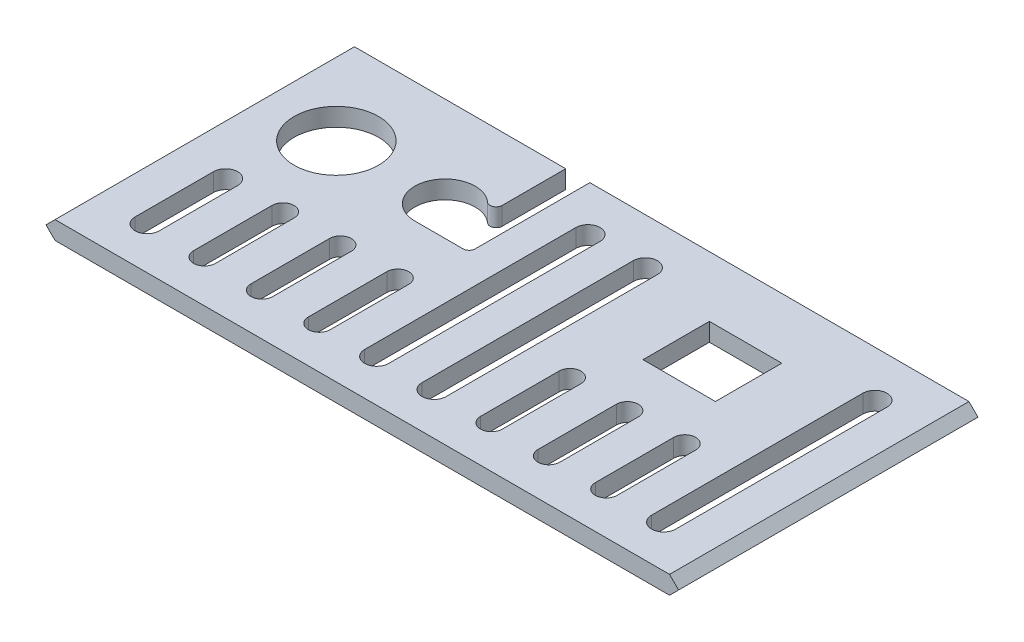
SolidWorks part; units mm, degrees
ref_plane "前视基准面" through (0, 0, 0) normal (0, 0, 1) x (1, 0, 0)
ref_plane "上视基准面" through (0, 0, 0) normal (0, 1, 0) x (1, 0, 0)
ref_plane "右视基准面" through (0, 0, 0) normal (1, 0, 0) x (0, 0, -1)
sketch "Sketch4" plane through (0, 0, 0) normal (0, 0, 1) x (1, 0, 0)
  line L0 (-50.9, 0) -> (50.9, 0)
  line L1 (-50.9, 0) -> (-52.4, -1.5)
  line L2 (-52.4, -1.5) -> (-50.9, -3)
  line L3 (-50.9, -3) -> (50.9, -3)
  line L4 (50.9, -3) -> (52.4, -1.5)
  line L5 (52.4, -1.5) -> (50.9, 0)
  line L6 (0, 0) -> (0, -3) construction
  dimension "D1" = 3
  dimension "D2" = 101.8
extrude "Boss-Extrude1" add sketch "Sketch4" along normal blind 49.6
sketch "Sketch5" plane through (0, 0, 0) normal (0, 1, 0) x (1, 0, 0)
  line L0 (17.9, -10) -> (29.9, -10)
  line L1 (17.9, -10) -> (17.9, -21)
  line L2 (17.9, -21) -> (29.9, -21)
  line L3 (29.9, -10) -> (29.9, -21)
  line L4 (-15.9, -15) -> (-15.9, 0)
  line L5 (-15.9, 0) -> (-11.9, 0)
  line L6 (-11.9, 0) -> (-11.9, -20)
  line L7 (-11.9, -20) -> (-20.9, -20)
  line L8 (-42.6561, -42.5938) -> (-42.6561, -29.5938) construction
  line L9 (-44.6561, -42.5938) -> (-44.6561, -29.5938)
  line L10 (42.9178, -42.5938) -> (42.9178, -7.5938) construction
  line L11 (40.9178, -42.5938) -> (40.9178, -7.5938)
  line L12 (44.9178, -42.5938) -> (44.9178, -7.5938)
  line L13 (-40.6561, -42.5938) -> (-40.6561, -29.5938)
  line L14 (-33.1461, -42.5938) -> (-33.1461, -29.5938) construction
  line L15 (-34.9655, -42.5938) -> (-34.9655, -29.5938)
  line L16 (-31.3266, -42.5938) -> (-31.3266, -29.5938)
  line L17 (-23.6384, -42.5938) -> (-23.6384, -29.5938) construction
  line L18 (-25.4578, -42.5938) -> (-25.4578, -29.5938)
  line L19 (-21.8189, -42.5938) -> (-21.8189, -29.5938)
  line L20 (-14.1307, -42.5938) -> (-14.1307, -29.5938) construction
  line L21 (-15.9501, -42.5938) -> (-15.9501, -29.5938)
  line L22 (-12.3112, -42.5938) -> (-12.3112, -29.5938)
  line L23 (-4.623, -42.5938) -> (-4.623, -7.5938) construction
  line L24 (-6.623, -42.5938) -> (-6.623, -7.5938)
  line L25 (-2.623, -42.5938) -> (-2.623, -7.5938)
  line L26 (4.8847, -42.5938) -> (4.8847, -7.5938) construction
  line L27 (2.8847, -42.5938) -> (2.8847, -7.5938)
  line L28 (6.8847, -42.5938) -> (6.8847, -7.5938)
  line L29 (14.3924, -42.5938) -> (14.3924, -29.5938) construction
  line L30 (12.5729, -42.5938) -> (12.5729, -29.5938)
  line L31 (16.2119, -42.5938) -> (16.2119, -29.5938)
  line L32 (23.9001, -42.5938) -> (23.9001, -29.5938) construction
  line L33 (22.0806, -42.5938) -> (22.0806, -29.5938)
  line L34 (25.7195, -42.5938) -> (25.7195, -29.5938)
  line L35 (33.4078, -42.5938) -> (33.4078, -29.5938) construction
  line L36 (31.5883, -42.5938) -> (31.5883, -29.5938)
  line L37 (35.2272, -42.5938) -> (35.2272, -29.5938)
  line L38 (-50.9, -49.6) -> (-50.9, 0) construction
  line L39 (50.9, 0) -> (-50.9, 0) construction
  line L40 (50.9, -49.6) -> (50.9, 0) construction
  arc A0 (-15.9, -15) -> (-20.9, -20) centre (-20.9, -15) ccw
  circle A1 centre (-38.9, -15) radius 7
  arc A2 (40.9178, -42.5938) -> (44.9178, -42.5938) centre (42.9178, -42.5938) ccw
  arc A3 (44.9178, -7.5938) -> (40.9178, -7.5938) centre (42.9178, -7.5938) ccw
  arc A4 (-44.6561, -42.5938) -> (-40.6561, -42.5938) centre (-42.6561, -42.5938) ccw
  arc A5 (-34.9655, -42.5938) -> (-31.3266, -42.5938) centre (-33.1461, -42.5938) ccw
  arc A6 (-31.3266, -29.5938) -> (-34.9655, -29.5938) centre (-33.1461, -29.5938) ccw
  arc A7 (-25.4578, -42.5938) -> (-21.8189, -42.5938) centre (-23.6384, -42.5938) ccw
  arc A8 (-21.8189, -29.5938) -> (-25.4578, -29.5938) centre (-23.6384, -29.5938) ccw
  arc A9 (-15.9501, -42.5938) -> (-12.3112, -42.5938) centre (-14.1307, -42.5938) ccw
  arc A10 (-12.3112, -29.5938) -> (-15.9501, -29.5938) centre (-14.1307, -29.5938) ccw
  arc A11 (-6.623, -42.5938) -> (-2.623, -42.5938) centre (-4.623, -42.5938) ccw
  arc A12 (-2.623, -7.5938) -> (-6.623, -7.5938) centre (-4.623, -7.5938) ccw
  arc A13 (2.8847, -42.5938) -> (6.8847, -42.5938) centre (4.8847, -42.5938) ccw
  arc A14 (6.8847, -7.5938) -> (2.8847, -7.5938) centre (4.8847, -7.5938) ccw
  arc A15 (12.5729, -42.5938) -> (16.2119, -42.5938) centre (14.3924, -42.5938) ccw
  arc A16 (16.2119, -29.5938) -> (12.5729, -29.5938) centre (14.3924, -29.5938) ccw
  arc A17 (22.0806, -42.5938) -> (25.7195, -42.5938) centre (23.9001, -42.5938) ccw
  arc A18 (25.7195, -29.5938) -> (22.0806, -29.5938) centre (23.9001, -29.5938) ccw
  arc A19 (31.5883, -42.5938) -> (35.2272, -42.5938) centre (33.4078, -42.5938) ccw
  arc A20 (35.2272, -29.5938) -> (31.5883, -29.5938) centre (33.4078, -29.5938) ccw
  arc A21 (-40.6561, -29.5938) -> (-44.6561, -29.5938) centre (-42.6561, -29.5938) ccw
  point P14 (42.9178, -25.0938)
  point P22 (-42.6561, -36.0938)
  point P29 (-33.1461, -36.0938)
  point P36 (-23.6384, -36.0938)
  point P43 (-14.1307, -36.0938)
  point P50 (-4.623, -25.0938)
  point P57 (4.8847, -25.0938)
  point P64 (14.3924, -36.0938)
  point P71 (23.9001, -36.0938)
  point P77 (33.4078, -36.0938)
  dimension "D3" = 5
  dimension "D7" = 14
  dimension "D1" = 12
  dimension "D2" = 11
  dimension "D4" = 13
  dimension "D5" = 4
  dimension "D6" = 10
  dimension "D8" = 12
  dimension "D9" = 30
  dimension "D10" = 15
  dimension "D11" = 15
  dimension "D12" = 21
extrude "Cut-Extrude1" cut sketch "Sketch5" against normal up to next
fillet "Fillet1" radius 1 2 edges at (-11.9, -1.5, 20) (-15.9, -1.5, 15)
